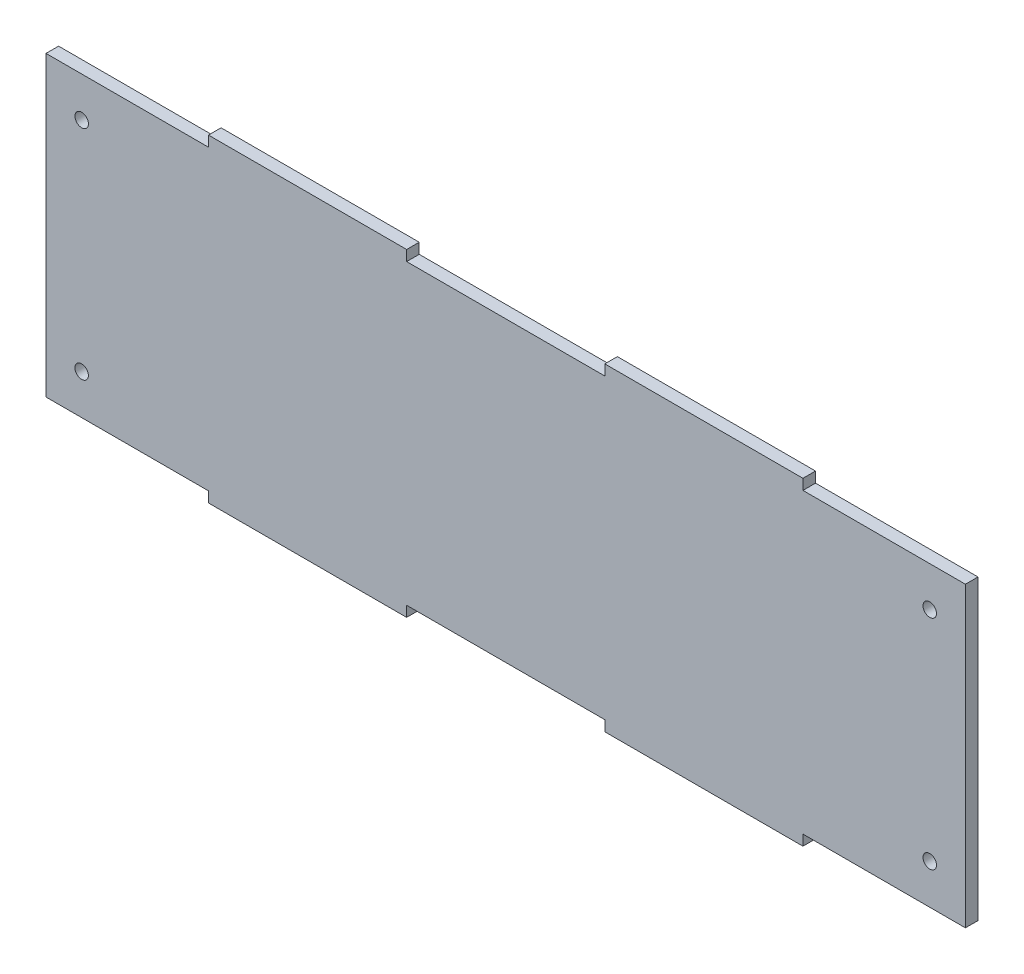
SolidWorks part; units mm, degrees
ref_plane "Front Plane" through (0, 0, 0) normal (0, 0, 1) x (1, 0, 0)
ref_plane "Top Plane" through (0, 0, 0) normal (0, 1, 0) x (1, 0, 0)
ref_plane "Right Plane" through (0, 0, 0) normal (1, 0, 0) x (0, 0, -1)
sketch "Sketch1" plane through (0, 0, 0) normal (0, 0, 1) x (1, 0, 0)
  line L0 (116, 75.1) -> (116, 0) construction
  line L1 (0, 0) -> (232, 0)
  line L2 (0, 0) -> (0, 75.1)
  line L3 (0, 75.1) -> (232, 75.1)
  line L4 (232, 0) -> (232, 75.1)
  line L5 (0, 37.55) -> (232, 37.55) construction
  circle A0 centre (9, 65.05) radius 1.7
  circle A2 centre (9, 10.05) radius 1.7
  circle A3 centre (223, 10.05) radius 1.7
  circle A4 centre (223, 65.05) radius 1.7
  dimension "D3" = 3.4
  dimension "D1" = 10.05
  dimension "D2" = 9
  dimension "D4" = 232
  dimension "D5" = 75.1
extrude "Boss-Extrude1" add sketch "Sketch1" along normal blind 3.175
sketch "Sketch2" plane through (0, 0, 3.175) normal (0, 0, 1) x (1, 0, 0)
  line L0 (0, 0) -> (232, 0) construction
  line L1 (41, 0) -> (91, 0)
  line L2 (41, 0) -> (41, -2.65)
  line L3 (41, -2.65) -> (91, -2.65)
  line L4 (91, 0) -> (91, -2.65)
  line L5 (232, 75.1) -> (0, 75.1) construction
  line L6 (41, 75.1) -> (91, 75.1)
  line L7 (41, 75.1) -> (41, 77.75)
  line L8 (41, 77.75) -> (91, 77.75)
  line L9 (91, 75.1) -> (91, 77.75)
  line L10 (66, -2.65) -> (66, 77.75) construction
  line L11 (116, 0) -> (116, 75.1) construction
  line L12 (191, 0) -> (191, -2.65)
  line L13 (191, 0) -> (141, 0)
  line L14 (141, 0) -> (141, -2.65)
  line L15 (191, -2.65) -> (141, -2.65)
  line L16 (191, 75.1) -> (191, 77.75)
  line L17 (191, 75.1) -> (141, 75.1)
  line L18 (191, 77.75) -> (141, 77.75)
  line L19 (141, 75.1) -> (141, 77.75)
  dimension "D1" = 50
  dimension "D2" = 2.65
  dimension "D3" = 25
extrude "Boss-Extrude2" add sketch "Sketch2" against normal up to surface (3.175 mm away) up to face at (224.7, 10.05, 0)
